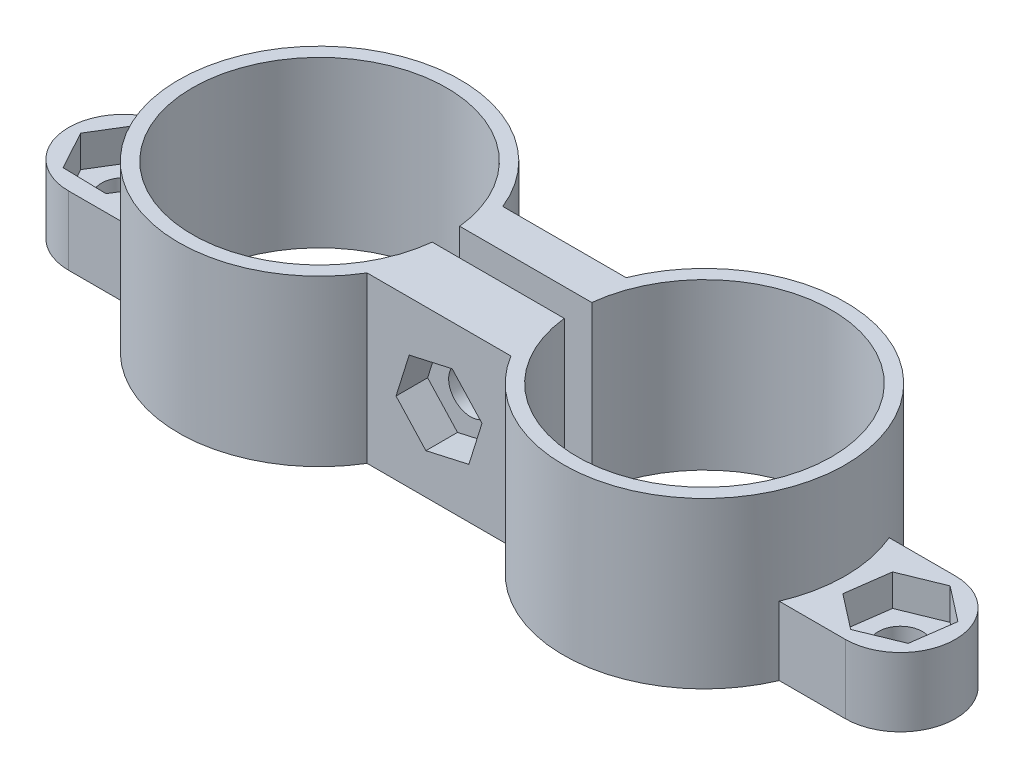
SolidWorks part; units mm, degrees
ref_plane "Front Plane" through (0, 0, 0) normal (0, 0, 1) x (1, 0, 0)
ref_plane "Top Plane" through (0, 0, 0) normal (0, 1, 0) x (1, 0, 0)
ref_plane "Right Plane" through (0, 0, 0) normal (1, 0, 0) x (0, 0, -1)
sketch "Sketch1" plane through (0, 0, 0) normal (0, 1, 0) x (1, 0, 0)
  line L0 (14, -1) -> (14, -33.4508) construction
  line L1 (9.514, 3.814) -> (18.486, 3.814) construction
  line L2 (9.1958, 1) -> (18.8042, 1) construction
  line L3 (0, 0) -> (59.6408, 0) construction
  line L4 (9.1958, -1) -> (18.8042, -1) construction
  line L5 (0, 0) -> (-34.7594, 0) construction
  line L6 (9.1958, 1) -> (18.8042, 1)
  line L7 (9.1958, -1) -> (18.8042, -1)
  line L8 (9.514, 3.814) -> (18.486, 3.814)
  line L10 (-14.25, 4) -> (-9.4373, 4)
  line L11 (-14.25, -4) -> (-9.4373, -4)
  line L12 (42.25, 4) -> (37.4373, 4)
  line L13 (42.25, -4) -> (37.4373, -4)
  line L14 (8.7681, -5.3088) -> (19.2319, -5.3088)
  arc A0 (9.1958, 1) -> (9.1958, -1) centre (0, 0) ccw
  arc A1 (9.514, 3.814) -> (8.7681, -5.3088) centre (0, 0) ccw
  arc A2 (18.8042, 1) -> (18.8042, -1) centre (28, 0) cw
  arc A3 (18.486, 3.814) -> (19.2319, -5.3088) centre (28, 0) cw
  arc A4 (-14.25, 4) -> (-14.25, -4) centre (-14.25, 0) ccw
  circle A5 centre (-14.25, 0) radius 1.6
  circle A6 centre (42.25, 0) radius 1.6
  arc A7 (42.25, 4) -> (42.25, -4) centre (42.25, 0) cw
  dimension "D1" = 18.5
  dimension "D2" = 20.5
  dimension "D4" = 3.2
  dimension "D5" = 8
  dimension "D3" = 14
  dimension "D6" = 14.25
extrude "Boss-Extrude2" add sketch "Sketch1" along normal blind 5 contours L10 A4 L11 A1 A5 | A7 L12 A3 L13 A6 region at (-10.369, 0, 0) region at (39.8436, 0, -3.881)
extrude "Boss-Extrude3" add sketch "Sketch1<4>" along normal blind 12 contours A3 L8 A1 L6 A2 L7 A0 region at (14, 0, -3.2874)
sketch "Sketch1<4>" plane through (0, 0, 0) normal (0, 1, 0) x (1, 0, 0) same geometry as "Sketch1"
sketch "Sketch2" plane through (0, 5, 0) normal (0, 1, 0) x (1, 0, 0)
  line L1 (-15.782, 2.8143) -> (-17.4533, 0.0804)
  line L2 (-17.4533, 0.0804) -> (-15.9212, -2.7339)
  line L3 (-15.9212, -2.7339) -> (-12.718, -2.8143)
  line L4 (-12.718, -2.8143) -> (-11.0467, -0.0804)
  line L5 (-11.0467, -0.0804) -> (-12.5788, 2.7339)
  line L6 (-12.5788, 2.7339) -> (-15.782, 2.8143)
  circle A0 centre (-14.25, 0) radius 2.775 construction
  dimension "D1" = 5.55
extrude "Cut-Extrude1" cut sketch "Sketch2" against normal blind 2.3
sketch "Sketch3" plane through (0, 5, 0) normal (0, 1, 0) x (1, 0, 0)
  line L1 (42.687, 3.1802) -> (39.7144, 1.9686)
  line L2 (39.7144, 1.9686) -> (39.2774, -1.2116)
  line L3 (39.2774, -1.2116) -> (41.813, -3.1802)
  line L4 (41.813, -3.1802) -> (44.7856, -1.9686)
  line L5 (44.7856, -1.9686) -> (45.2226, 1.2116)
  line L6 (45.2226, 1.2116) -> (42.687, 3.1802)
  circle A0 centre (42.25, 0) radius 2.78 construction
  dimension "D1" = 5.56
extrude "Cut-Extrude2" cut sketch "Sketch3" against normal blind 2.3
sketch "Sketch4" plane through (0, 0, 5.3088) normal (0, 0, 1) x (1, 0, 0)
  line L0 (8.7681, 12) -> (19.2319, 0) construction
  line L1 (19.2319, 12) -> (8.7681, 0) construction
  circle A0 centre (14, 6) radius 1.6
extrude "Cut-Extrude3" cut sketch "Sketch4" against normal blind 15
sketch "Sketch7" plane through (0, 0, 5.3088) normal (0, 0, 1) x (1, 0, 0)
  line L1 (14.9546, 9.0588) -> (11.8283, 8.3561)
  line L2 (11.8283, 8.3561) -> (10.8737, 5.2973)
  line L3 (10.8737, 5.2973) -> (13.0454, 2.9412)
  line L4 (13.0454, 2.9412) -> (16.1717, 3.6439)
  line L5 (16.1717, 3.6439) -> (17.1263, 6.7027)
  line L6 (17.1263, 6.7027) -> (14.9546, 9.0588)
  circle A0 centre (14, 6) radius 2.775 construction
  dimension "D1" = 5.55
extrude "Cut-Extrude4" cut sketch "Sketch7" against normal blind 2.3
